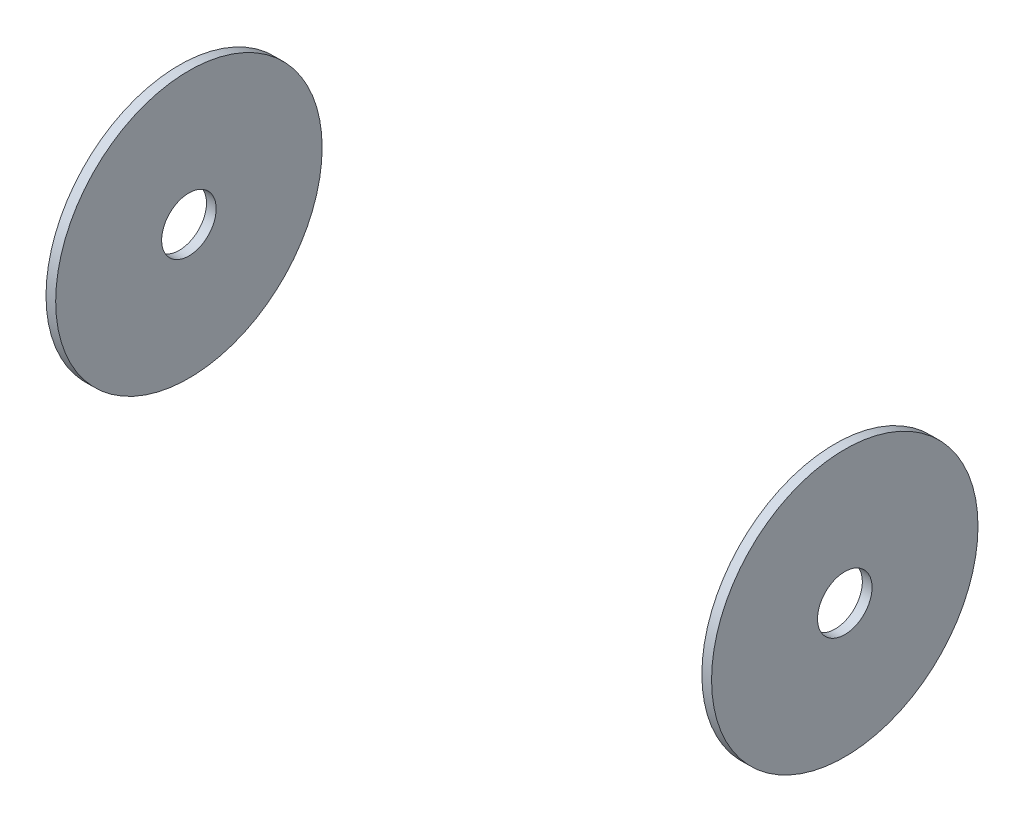
SolidWorks part; units mm, degrees
material "Titanium"
ref_plane "Front Plane" through (0, 0, 0) normal (0, 0, 1) x (1, 0, 0)
ref_plane "Top Plane" through (0, 0, 0) normal (0, 1, 0) x (1, 0, 0)
ref_plane "Right Plane" through (0, 0, 0) normal (1, 0, 0) x (0, 0, -1)
sketch "Sketch1" plane through (50.05, 0, 0) normal (1, 0, 0) x (0, 0, -1)
  circle A0 centre (-177.8, 26.9875) radius 20.6375
  arc A1 (-196.4827, 35.7546) -> (-198.0575, 23.0453) centre (-177.8, 26.9875) ccw construction
  circle A2 centre (-177.8, 26.9875) radius 4.2227
  dimension "D1" = 8.4455
extrude "Boss-Extrude1" add sketch "Sketch1" along normal blind 1.5
mirror "Mirror2" about plane through (0, 0, 0) normal (1, 0, 0) of bodies 101
equation "\"weapon shaft threads\"= 5 / 16"
equation "\"D1@Sketch1\"=\"weapon shaft threads\" + .02in"
equation "\"D1@Boss-Extrude1\"=1.5mm"
